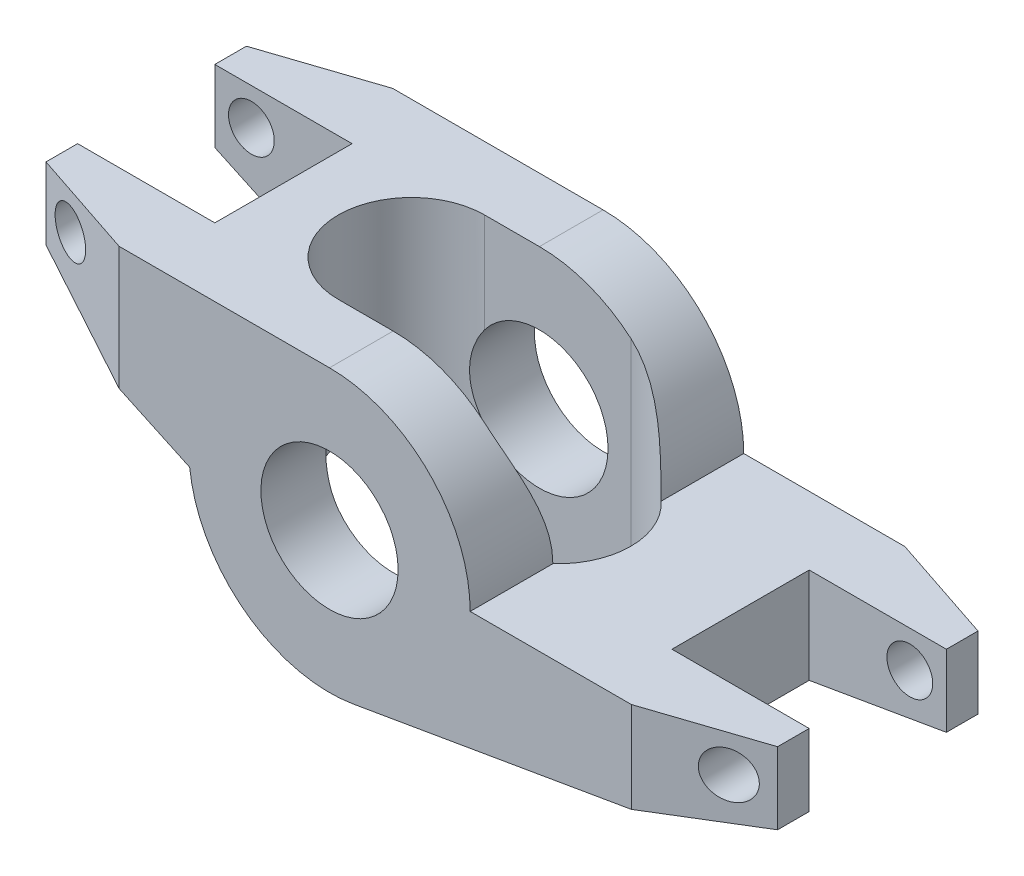
SolidWorks part; units mm, degrees
ref_plane "Front Plane" through (0, 0, 0) normal (0, 0, 1) x (1, 0, 0)
ref_plane "Top Plane" through (0, 0, 0) normal (0, 1, 0) x (1, 0, 0)
ref_plane "Right Plane" through (0, 0, 0) normal (1, 0, 0) x (0, 0, -1)
sketch "Sketch1" plane through (0, 0, 0) normal (0, 0, 1) x (1, 0, 0)
  line L0 (1.6553, -9.6287) -> (28.58, -5)
  line L1 (28.58, -5) -> (28.58, 0)
  line L2 (28.58, 0) -> (9.77, 0)
  line L3 (0, 9.77) -> (-22.23, 9.77)
  line L4 (-22.23, 9.77) -> (-22.23, 4.77)
  line L5 (-22.23, 4.77) -> (-9.7115, -1.0675)
  circle A0 centre (0, 0) radius 4.765
  arc A1 (9.77, 0) -> (0, 9.77) centre (0, 0) ccw
  arc A2 (-9.7115, -1.0675) -> (1.6553, -9.6287) centre (0, 0) ccw
  circle A3 centre (26.04, -2.54) radius 1.59
  circle A4 centre (-19.69, 7.23) radius 1.59
  point P14 (0, 0)
  point P17 (0, 0)
  dimension "D1" = 9.53
  dimension "D2" = 19.54
  dimension "D8" = 3.18
  dimension "D9" = 2.54
  dimension "D10" = 2.54
  dimension "D3" = 28.58
  dimension "D4" = 5
  dimension "D5" = 5
  dimension "D6" = 25
  dimension "D7" = 22.23
  dimension "D11" = 2.54
  dimension "D12" = 2.54
extrude "Boss-Extrude1" add sketch "Sketch1" along normal mid plane 19
chamfer "Chamfer1" distance 7.62 distance2 2.54 3 edges at (28.58, -2.5, -9.5) (-22.23, 7.27, 9.5) (-22.23, 7.27, -9.5) first distance on face at (1.8234, 1.0227, -9.5) first distance on face at (-18.1, 7.23, 9.5)
chamfer "Chamfer2" distance 2.54 distance2 7.62 1 edges at (28.58, -2.5, 9.5) first distance on face at (28.58, -2.5, 1.27)
sketch "Sketch3" plane through (0, 0, 0) normal (0, 1, 0) x (1, 0, 0)
  line L0 (-22.23, -6.96) -> (-22.23, 6.96) construction
  line L1 (-12.7, -4.765) -> (-22.23, -4.765)
  line L2 (-12.7, -4.765) -> (-12.7, 4.765)
  line L3 (-12.7, 4.765) -> (-22.23, 4.765)
  line L4 (-22.23, -4.765) -> (-22.23, 4.765)
  line L5 (-12.7, -4.765) -> (-22.23, 4.765) construction
  line L6 (-12.7, 4.765) -> (-22.23, -4.765) construction
  line L7 (28.58, -6.96) -> (28.58, 6.96) construction
  line L8 (19.05, 4.765) -> (28.58, 4.765)
  line L9 (19.05, 4.765) -> (19.05, -4.765)
  line L10 (19.05, -4.765) -> (28.58, -4.765)
  line L11 (28.58, 4.765) -> (28.58, -4.765)
  line L12 (19.05, 4.765) -> (28.58, -4.765) construction
  line L13 (19.05, -4.765) -> (28.58, 4.765) construction
  point P0 (-17.465, 0)
  point P7 (23.815, 0)
  dimension "D1" = 9.53
  dimension "D2" = 9.53
  dimension "D3" = 9.53
  dimension "D4" = 9.53
extrude "Cut-Extrude1" cut sketch "Sketch3" against normal through all both and the other way through all
sketch "Sketch2" plane through (0, 9.77, 0) normal (0, 1, 0) x (1, 0, 0)
  line L0 (6.35, 0) -> (-3.81, 0) construction
  line L1 (-12.7, -4.765) -> (-12.7, 4.765) construction
  line L2 (6.35, -5.08) -> (-3.81, -5.08)
  line L3 (6.35, 5.08) -> (-3.81, 5.08)
  arc A0 (6.35, -5.08) -> (6.35, 5.08) centre (6.35, 0) ccw
  arc A1 (-3.81, 5.08) -> (-3.81, -5.08) centre (-3.81, 0) ccw
  point P2 (0, 0)
  point P5 (1.27, 0)
  dimension "D1" = 10.16
  dimension "D2" = 10.16
  dimension "D3" = 8.89
extrude "Cut-Extrude2" cut sketch "Sketch2" against normal through all
